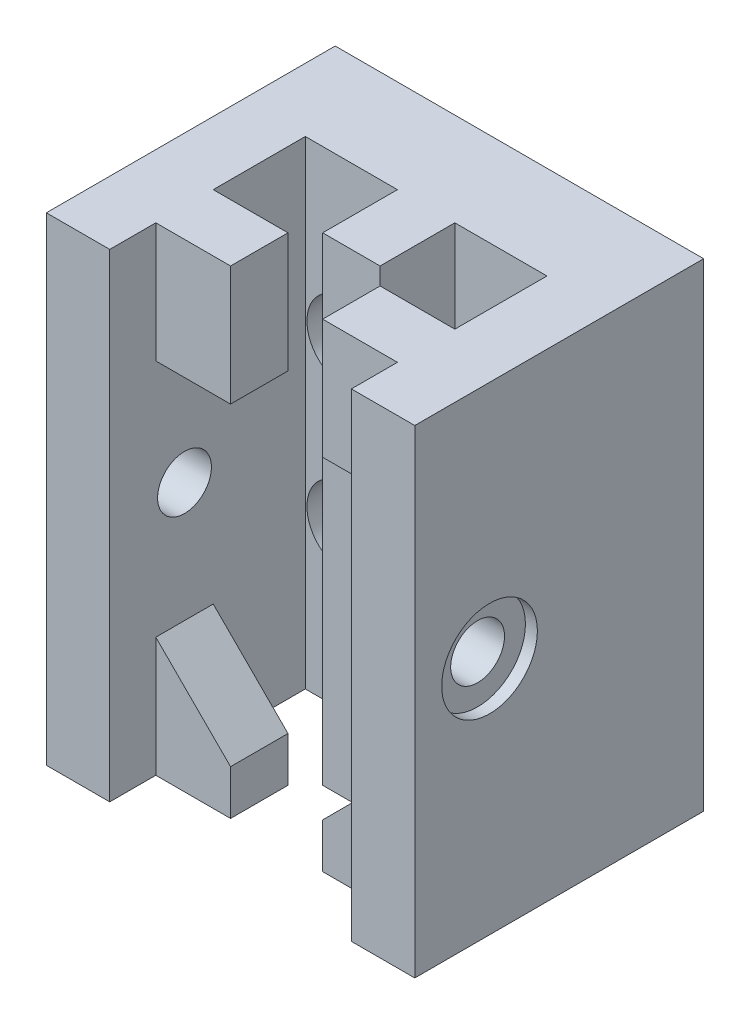
SolidWorks part; units mm, degrees
ref_plane "Plan de face" through (0, 0, 0) normal (0, 0, 1) x (1, 0, 0)
ref_plane "Plan de dessus" through (0, 0, 0) normal (0, 1, 0) x (1, 0, 0)
ref_plane "Plan de droite" through (0, 0, 0) normal (1, 0, 0) x (0, 0, -1)
sketch "Base" plane through (0, 0, 0) normal (0, 1, 0) x (1, 0, 0)
  line L0 (-3.85, -2.4) -> (-3.85, 2.4)
  line L1 (-3.85, 2.4) -> (-10.1, 2.4)
  line L2 (-10.1, 2.4) -> (-10.1, 10.1)
  line L3 (-10.1, 10.1) -> (-2.4, 10.1)
  line L4 (-2.4, 10.1) -> (-2.4, 3.85)
  line L5 (-2.4, 3.85) -> (2.4, 3.85)
  line L6 (0, -55) -> (0, 55) construction
  line L7 (2.4, 10.1) -> (2.4, 3.85)
  line L8 (10.1, 10.1) -> (2.4, 10.1)
  line L9 (10.1, 2.4) -> (10.1, 10.1)
  line L10 (3.85, 2.4) -> (10.1, 2.4)
  line L11 (3.85, -2.4) -> (3.85, 2.4)
  line L12 (-55, 0) -> (55, 0) construction
  line L13 (3.85, -2.4) -> (10.1, -2.4)
  line L14 (10.1, -2.4) -> (10.1, -6.25)
  line L20 (-10.1, -2.4) -> (-10.1, -6.25)
  line L21 (-3.85, -2.4) -> (-10.1, -2.4)
  line L23 (-15.4, 15.4) -> (15.4, 15.4)
  line L24 (-15.4, 15.4) -> (-15.4, -6.25)
  line L26 (15.4, 15.4) -> (15.4, -6.25)
  line L27 (-15.4, 15.4) -> (0, 0) construction
  line L28 (0, 0) -> (15.4, 15.4) construction
  line L29 (-10.1, -6.25) -> (-15.4, -6.25)
  line L30 (10.1, -6.25) -> (15.4, -6.25)
  line L31 (10.1, -10.1) -> (15.4, -15.4) construction
  point P2 (-3.85, 0)
  point P3 (0, 3.85)
  point P27 (0, 0)
  dimension "D1" = 4.8
  dimension "D2" = 4.8
  dimension "D3" = 6.25
  dimension "D4" = 7.7
  dimension "D5" = 30.8
extrude "Boss.-Extru.1" add sketch "Base" along normal mid plane 40
hole_wizard "Chambrage pour vis à six pans creux M41" positions "Esquisse4" profile "Esquisse5" counterbore size "M4" standard "ISO" end condition up to next
sketch "Esquisse4" plane through (15.4, 0, 0) normal (1, 0, 0) x (0, 0, -1)
  point P0 (0, 0)
sketch "Esquisse5" plane through (15.4, 0, 0) normal (0, 1, 0) x (0, 0, -1)
  line L0 (0, 0) -> (0, 11.55)
  line L1 (0, 11.55) -> (2.25, 11.55)
  line L3 (2.25, 11.55) -> (2.25, 1)
  line L4 (2.25, 1) -> (4, 1)
  line L5 (4, 1) -> (4, 0)
  line L7 (4, 0) -> (0, 0)
  line L11 (0, -6.35) -> (0, 107.95) construction
  dimension "Diamètre du perçage jusqu'au prochain" = 4.5
  dimension "Profondeur du perçage jusqu'au prochain" = 11.55
  dimension "Diamètre du chambrage" = 8
  dimension "Profondeur du chambrage" = 1
mirror "Symétrie1" about plane through (0, 0, 0) normal (1, 0, 0) of "Chambrage pour vis à six pans creux M41"
sketch "Esquisse6" plane through (0, 0, 0) normal (0, 0, 1) x (1, 0, 0)
  line L0 (10.1, 20) -> (10.1, -20) construction
  line L1 (-10.1, 10) -> (10.1, 10)
  line L2 (-10.1, 10) -> (-10.1, -10)
  line L3 (-10.1, -10) -> (10.1, -10)
  line L4 (10.1, 10) -> (10.1, -10)
  line L5 (-10.1, 10) -> (10.1, -10) construction
  line L6 (-10.1, -10) -> (10.1, 10) construction
  point P0 (0, 0)
  dimension "D1" = 20
extrude "Enlèv. mat.-Extru.1" cut sketch "Esquisse6" against normal mid plane 6
sketch "Esquisse7" plane through (0, 0, -10.1) normal (0, 0, 1) x (1, 0, 0)
  line L1 (-6.7175, 6.7175) -> (6.7175, 6.7175) construction
  line L2 (-6.7175, 6.7175) -> (-6.7175, -6.7175) construction
  line L3 (-6.7175, -6.7175) -> (6.7175, -6.7175) construction
  line L4 (6.7175, 6.7175) -> (6.7175, -6.7175) construction
  line L5 (-6.7175, 6.7175) -> (6.7175, -6.7175) construction
  line L6 (-6.7175, -6.7175) -> (6.7175, 6.7175) construction
  circle A0 centre (0, 0) radius 9.5 construction
  dimension "D1" = 19
sketch "Esquisse14" plane through (0, -20, 0) normal (0, -1, 0) x (1, 0, 0)
  line L0 (15.4, 6.25) -> (15.4, -15.4) construction
  line L1 (-15.4, -15.4) -> (15.4, -15.4)
  line L2 (-15.4, -15.4) -> (-15.4, -17.9)
  line L3 (-15.4, -17.9) -> (15.4, -17.9)
  line L4 (15.4, -15.4) -> (15.4, -17.9)
  dimension "D1" = 2.5
extrude "Boss.-Extru.3" add sketch "Esquisse14" against normal up to vertex (40 mm away) up to point (-15.4, 20, -15.4)
hole_wizard "Chambrage pour vis à six pans creux M31" positions "Esquisse10" profile "Esquisse12" counterbore size "M3" standard "ISO" end condition up to next
sketch "Esquisse10" plane through (0, 0, -10.1) normal (0, 0, 1) x (1, 0, 0)
  point P0 (-6.7175, 6.7175)
  point P3 (-6.7175, -6.7175)
  point P7 (6.7175, 6.7175)
  point P10 (6.7175, -6.7175)
sketch "Esquisse12" plane through (-6.7175, 6.7175, -10.1) normal (1, 0, 0) x (0, -1, 0)
  line L0 (0, 0) -> (0, 7.8)
  line L1 (0, 7.8) -> (1.7, 7.8)
  line L3 (1.7, 7.8) -> (1.7, 3.4)
  line L4 (1.7, 3.4) -> (3.25, 3.4)
  line L5 (3.25, 3.4) -> (3.25, 0)
  line L7 (3.25, 0) -> (0, 0)
  line L11 (0, -6.35) -> (0, 107.95) construction
  dimension "Diamètre du perçage jusqu'au prochain" = 3.4
  dimension "Profondeur du perçage jusqu'au prochain" = 7.8
  dimension "Diamètre du chambrage" = 6.5
  dimension "Profondeur du chambrage" = 3.4
chamfer "Chanfrein1" distance 6.25 angle 45 2 edges at (3.85, -10, 0) (-3.85, -10, 0)
